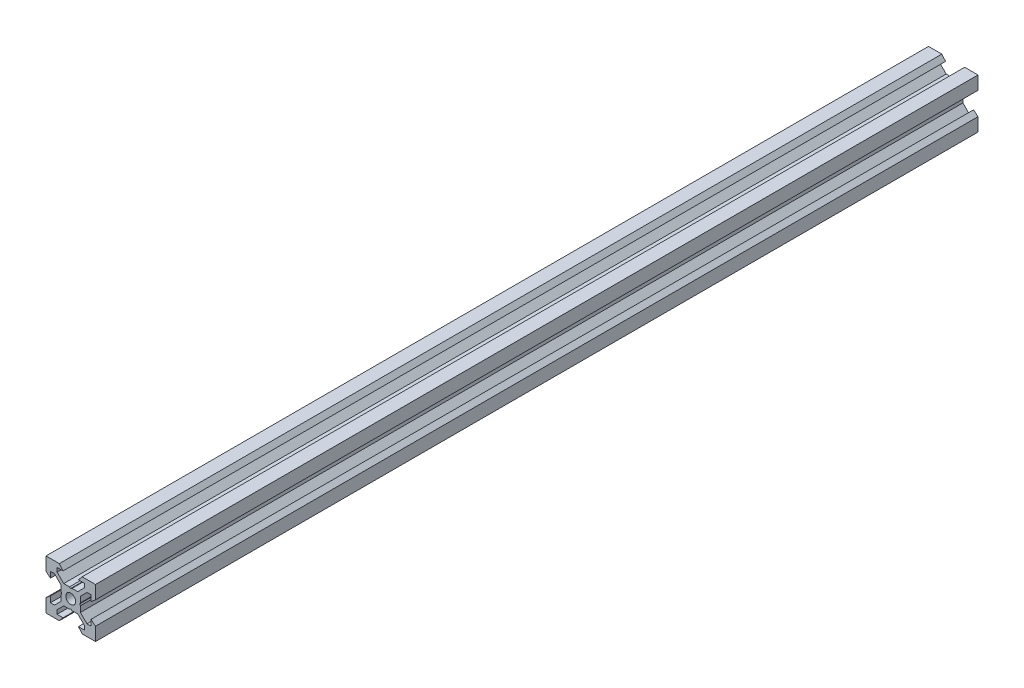
SolidWorks part; units mm, degrees
ref_plane "Front Plane" through (0, 0, 0) normal (0, 0, 1) x (1, 0, 0)
ref_plane "Top Plane" through (0, 0, 0) normal (0, 1, 0) x (1, 0, 0)
ref_plane "Right Plane" through (0, 0, 0) normal (1, 0, 0) x (0, 0, -1)
sketch "Sketch1" plane through (0, 0, 0) normal (0, 0, 1) x (1, 0, 0)
  line L0 (10, 10) -> (4.6104, 10) construction
  line L1 (10, 10) -> (10, 4.6104) construction
  line L2 (10, -10) -> (10, -4.6104) construction
  line L3 (10, -10) -> (4.6104, -10) construction
  line L4 (10, 10) -> (10, 4.6104)
  line L5 (6.5607, 5.5) -> (8.2, 5.5)
  line L6 (5.5, 8.2) -> (5.5, 6.5607)
  line L7 (10, 10) -> (4.6104, 10)
  line L8 (10, 10) -> (10, 4.6104)
  line L9 (6.5607, 5.5) -> (3.9, 2.8393)
  line L10 (5.5, 6.5607) -> (2.8393, 3.9)
  line L11 (10, 4.6104) -> (8.2, 3.1)
  line L12 (4.6104, 10) -> (3.1, 8.2)
  line L13 (8.2, 3.1) -> (8.2, 5.5)
  line L14 (3.1, 8.2) -> (5.5, 8.2)
  line L15 (-6.5607, 5.5) -> (-8.2, 5.5)
  line L16 (6.5607, -5.5) -> (8.2, -5.5)
  line L17 (3.1, -8.2) -> (5.5, -8.2)
  line L18 (8.2, -3.1) -> (8.2, -5.5)
  line L19 (4.6104, -10) -> (3.1, -8.2)
  line L20 (10, -4.6104) -> (8.2, -3.1)
  line L21 (0.5196, -3.9) -> (0, -3.6)
  line L22 (0.5196, 3.9) -> (0, 3.6)
  line L23 (3.6, 0) -> (3.9, -0.5196)
  line L24 (3.9, 0.5196) -> (3.6, 0)
  line L25 (3.9, 0.5196) -> (3.9, 2.8393)
  line L26 (2.8393, 3.9) -> (0.5196, 3.9)
  line L27 (3.9, -2.8393) -> (3.9, -0.5196)
  line L28 (2.8393, -3.9) -> (0.5196, -3.9)
  line L29 (5.5, -6.5607) -> (2.8393, -3.9)
  line L30 (6.5607, -5.5) -> (3.9, -2.8393)
  line L31 (10, -10) -> (10, -4.6104)
  line L32 (10, -10) -> (4.6104, -10)
  line L33 (5.5, -8.2) -> (5.5, -6.5607)
  line L34 (-6.5607, -5.5) -> (-8.2, -5.5)
  line L35 (10, -10) -> (10, -4.6104)
  line L36 (0, 0) -> (0, 8.2) construction
  line L37 (-10, -10) -> (-4.6104, -10) construction
  line L38 (-10, -10) -> (-10, -4.6104) construction
  line L39 (-10, 10) -> (-10, 4.6104) construction
  line L40 (-10, 10) -> (-4.6104, 10) construction
  line L41 (-10, -10) -> (-10, -4.6104)
  line L43 (-5.5, -8.2) -> (-5.5, -6.5607)
  line L44 (-10, -10) -> (-4.6104, -10)
  line L45 (-10, -10) -> (-10, -4.6104)
  line L46 (-6.5607, -5.5) -> (-3.9, -2.8393)
  line L47 (-5.5, -6.5607) -> (-2.8393, -3.9)
  line L48 (-2.8393, -3.9) -> (-0.5196, -3.9)
  line L49 (-3.9, -2.8393) -> (-3.9, -0.5196)
  line L50 (-2.8393, 3.9) -> (-0.5196, 3.9)
  line L51 (-3.9, 0.5196) -> (-3.9, 2.8393)
  line L52 (-3.9, 0.5196) -> (-3.6, 0)
  line L53 (-3.6, 0) -> (-3.9, -0.5196)
  line L54 (-0.5196, 3.9) -> (0, 3.6)
  line L55 (-0.5196, -3.9) -> (0, -3.6)
  line L56 (-10, -4.6104) -> (-8.2, -3.1)
  line L57 (-4.6104, -10) -> (-3.1, -8.2)
  line L58 (-8.2, -3.1) -> (-8.2, -5.5)
  line L59 (-3.1, -8.2) -> (-5.5, -8.2)
  line L60 (-10, -10) -> (10, -10) construction
  line L61 (-10, -10) -> (-10, 10) construction
  line L62 (-3.1, 8.2) -> (-5.5, 8.2)
  line L63 (-8.2, 3.1) -> (-8.2, 5.5)
  line L64 (-4.6104, 10) -> (-3.1, 8.2)
  line L65 (-10, 4.6104) -> (-8.2, 3.1)
  line L66 (-5.5, 6.5607) -> (-2.8393, 3.9)
  line L67 (-6.5607, 5.5) -> (-3.9, 2.8393)
  line L68 (-10, 10) -> (-10, 4.6104)
  line L69 (-10, 10) -> (-4.6104, 10)
  line L70 (-5.5, 8.2) -> (-5.5, 6.5607)
  line L71 (-10, 10) -> (10, 10) construction
  line L72 (-10, 10) -> (-10, 4.6104)
  line L73 (10, -10) -> (10, 10) construction
  line L74 (-10, -10) -> (10, 10) construction
  line L75 (-10, 10) -> (10, -10) construction
  circle A0 centre (0, 0) radius 2
  dimension "D7" = 4
  dimension "D1" = 20
  dimension "D2" = 5.3896
  dimension "D3" = 4.5
  dimension "D4" = 50
  dimension "D5" = 1.8
  dimension "D6" = 1.5104
  dimension "D8" = 5.5
  dimension "D9" = 120
  dimension "D10" = 0.3
  dimension "D11" = 2.3197
  dimension "D12" = 7.8
  dimension "D13" = 7.8
  dimension "D14" = 1.5
  dimension "D15" = 2.6607
extrude "Boss-Extrude1" add sketch "Sketch1" along normal mid plane 356.69 contours L70 L62 L64 L69 L68 L65 L63 L15 L67 L51 L52 L53 L49 L46 L34 L58 L56 L41 L44 L57 L59 L43 L47 L48 L55 L21 L28 L29 L33 L17 L19 L32 L31 L20 L18 L16 L30 L27 L23 L24 L25 L9 L5 L13 L11 L4 L7 L12 L14 L6 L10 region at (9.7172, 7.3052, 0)
